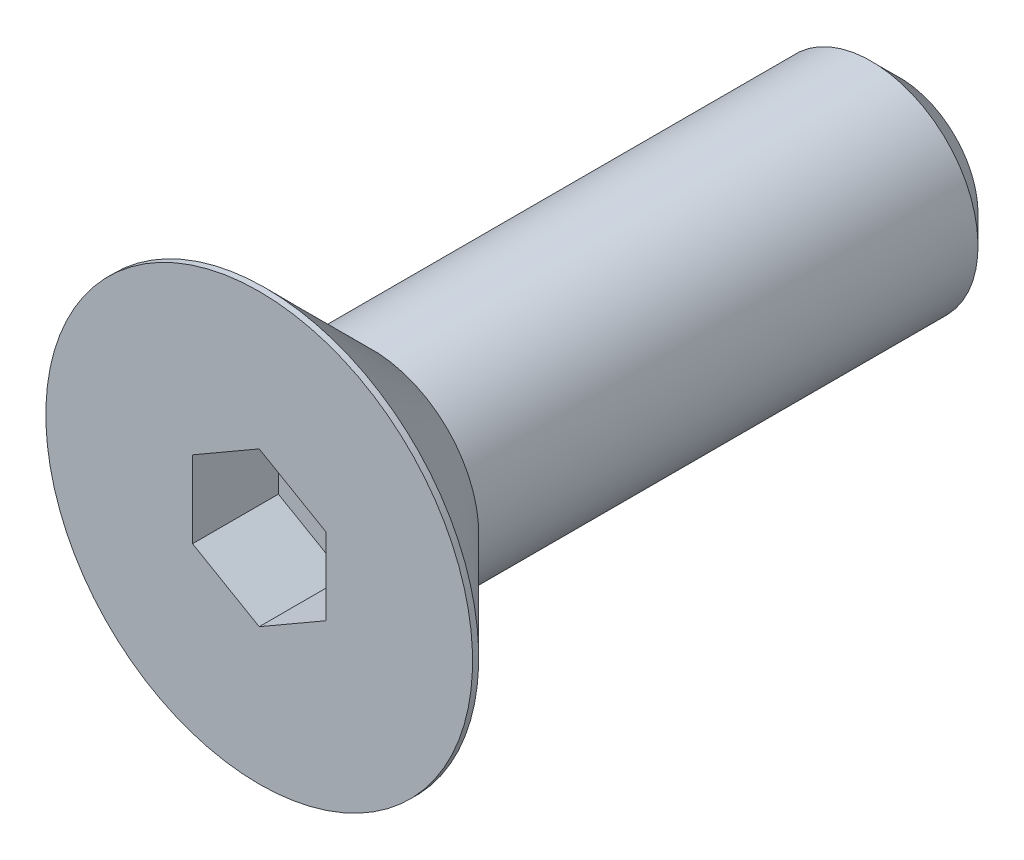
SolidWorks part; units mm, degrees
material "Chrome Stainless Steel"
ref_plane "Front" through (0, 0, 0) normal (0, 0, 1) x (1, 0, 0)
ref_plane "Top" through (0, 0, 0) normal (0, 1, 0) x (1, 0, 0)
ref_plane "Right" through (0, 0, 0) normal (1, 0, 0) x (0, 0, -1)
sketch "Sketch11" plane through (0, 0, 0) normal (1, 0, 0) x (0, 0, -1)
  line L0 (-6, 4) -> (6, 4) construction
  line L5 (-6, 4) -> (-6, -4) construction
  line L6 (6, 2) -> (6, -2) construction
  line L7 (-5.99, 1.25) -> (-5.99, -1.25) construction
  line L8 (5.9562, 2.0758) -> (6.6562, 2.0758) construction
  line L9 (6.6562, 2.0758) -> (6.3062, 1.4696) construction
  line L10 (6.3062, 1.4696) -> (5.9562, 2.0758) construction
  line L11 (6.2625, 1.5453) -> (6.35, 1.5453) construction
  line L12 (6.3062, 1.5453) -> (6.3062, 1.4696) construction
  line L13 (5.9781, 2.0379) -> (6.6344, 2.0379) construction
  line L14 (6.3062, 2.0758) -> (6.3062, 2) construction
  line L15 (6, 2) -> (6.6125, 2) construction
  line L17 (-5.885, 4) -> (-1.885, 0) construction
  line L18 (-1.885, 0) -> (-5.885, -4) construction
  point P3 (-3.7, 4)
  point P8 (0, 4)
  point P21 (6.3062, 2.0379)
  point P26 (-6, 0)
  point P28 (-5.99, 0)
  point P29 (6, 0)
  dimension "Length" = 12
  dimension "Head Diameter" = 8
  dimension "Thread Major Diameter" = 4
  dimension "Head Height" = 2.3
  dimension "Drive Size" = 2.5
  dimension "Thread Pitch" = 0.7
  dimension "D1" = 0.0875
  dimension "D2" = 0.01
  dimension "D3" = 0.115
  dimension "Countersink Angle" = 90
sketch "Sketch1" plane through (0, 0, 0) normal (1, 0, 0) x (0, 0, -1)
  line L2 (-3.7, 2) -> (6, 2)
  line L3 (6, 2) -> (6, 0)
  line L4 (-4.39, 2) -> (-4.39, 0)
  line L5 (-3.7, 2) -> (-4.39, 2)
  line L6 (-6, 4) -> (-6, -4) construction
  line L7 (6, 2) -> (6, -2) construction
  line L8 (-4.39, 0) -> (6, 0)
  dimension "D1" = 1.61
revolve "Revolve1" add sketch "Sketch1" angle 360 mid plane about L8
chamfer "Chamfer1" distance 0.525 angle 45 1 edges at (0, -2, -6)
sketch "Sketch7" plane through (0, 0, 0) normal (1, 0, 0) x (0, 0, -1)
  line L2 (-6, 4) -> (-5.885, 4)
  line L5 (-3.7, 1.815) -> (-3.7, 0)
  line L6 (-6, 4) -> (-6, 0)
  line L8 (-6, 4) -> (-6, -4) construction
  line L9 (-6, 0) -> (-3.7, 0)
  line L12 (-5.885, 4) -> (-3.7, 1.815)
  line L13 (-5.885, 4) -> (-1.885, 0) construction
revolve "Revolve2" add sketch "Sketch7" angle 360 mid plane about L9 region at (0, 1.5544, 4.9977)
ref_plane "Plane1" through (0, 0, 3.7) normal (0, 0, 1) x (1, 0, 0)
sketch "Sketch5" plane through (0, 0, 6) normal (0, 0, 1) x (1, 0, 0)
  line L1 (1.25, -0.7217) -> (1.25, 0.7217)
  line L2 (1.25, 0.7217) -> (0, 1.4434)
  line L3 (0, 1.4434) -> (-1.25, 0.7217)
  line L4 (-1.25, 0.7217) -> (-1.25, -0.7217)
  line L5 (-1.25, -0.7217) -> (0, -1.4434)
  line L6 (0, -1.4434) -> (1.25, -0.7217)
  circle A0 centre (0, 0) radius 1.25 construction
extrude "Cut-Extrude2" cut sketch "Sketch5" against normal blind 1.61
sketch "Sketch6" plane through (0, 0, 6) normal (0, 0, -1) x (-1, 0, 0)
  circle A0 centre (0, 0) radius 1.4434
extrude "Cut-Extrude3" [suppressed] cut sketch "Sketch6" along normal blind 1.61 draft 45
sketch "Sketch12" [suppressed] plane through (0, 0, -6) normal (0, 0, -1) x (-1, 0, 0)
  circle A0 centre (0, 0) radius 2 construction
  circle A1 centre (0, 0) radius 2
curve "Helix/Spiral1" [suppressed] pitch 0.7 height 12 turns 17.1429
sketch "Sketch13" [suppressed] plane through (0, 0, 0) normal (1, 0, 0) x (0, 0, -1)
  line L0 (5.9781, 2.0379) -> (6.6344, 2.0379)
  line L1 (6.6344, 2.0379) -> (6.35, 1.5453)
  line L2 (6.35, 1.5453) -> (6.2625, 1.5453)
  line L3 (6.2625, 1.5453) -> (5.9781, 2.0379)
sweep "Cut-Sweep1" [suppressed] cut profiles "Sketch13" path "Helix/Spiral1"
combine bodies "Combine1" [suppressed] operation type add bodies to combine 113 127
equation "\"D1@Chamfer1\"=\"Thread Pitch@Sketch11\" * .75"
equation "\"D1@Cut-Extrude2\"= \"Head Height@Sketch11\" * .7"
equation "\"D1@Cut-Extrude3\" = \"D1@Cut-Extrude2\""
equation "\"D1@Sketch11\"=\"Thread Pitch@Sketch11\"/8"
equation "\"D3@Sketch11\"=\"Head Height@Sketch11\"*.05"
equation "\"D4@Helix/Spiral1\"=\"Thread Pitch@Sketch11\""
equation "\"D1@Sketch1\"=\"Head Height@Sketch11\"*.7"
equation "\"D3@Helix/Spiral1\"=\"Length@Sketch11\""
